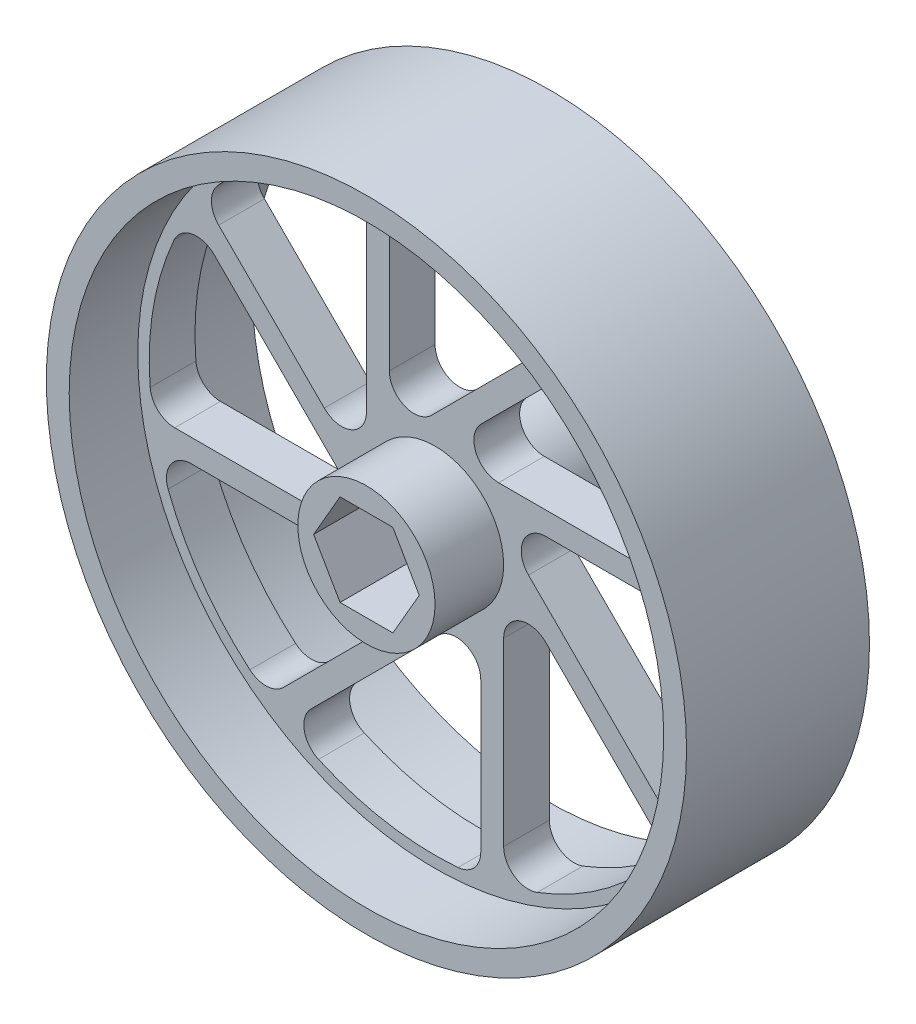
SolidWorks part; units mm, degrees
material "6061-T6 (SS)"
ref_plane "Front Plane" through (0, 0, 0) normal (0, 0, 1) x (1, 0, 0)
ref_plane "Top Plane" through (0, 0, 0) normal (0, 1, 0) x (1, 0, 0)
ref_plane "Right Plane" through (0, 0, 0) normal (1, 0, 0) x (0, 0, -1)
sketch "Sketch1" plane through (0, 0, 0) normal (0, 0, 1) x (1, 0, 0)
  line L1 (3.6662, -6.35) -> (7.3323, 0)
  line L2 (7.3323, 0) -> (3.6662, 6.35)
  line L3 (3.6662, 6.35) -> (-3.6662, 6.35)
  line L4 (-3.6662, 6.35) -> (-7.3323, 0)
  line L5 (-7.3323, 0) -> (-3.6662, -6.35)
  line L6 (-3.6662, -6.35) -> (3.6662, -6.35)
  circle A0 centre (0, 0) radius 44.45
  circle A1 centre (0, 0) radius 6.35 construction
  dimension "D1" = 88.9
  dimension "D2" = 12.7
extrude "Boss-Extrude1" add sketch "Sketch1" along normal mid plane 25.4
sketch "Sketch2" plane through (0, 0, 12.7) normal (0, 0, 1) x (1, 0, 0)
  circle A0 centre (0, 0) radius 9.525
  circle A1 centre (0, 0) radius 41.275
  circle A2 centre (0, 0) radius 44.45 construction
  dimension "D1" = 3.175
  dimension "D2" = 19.05
extrude "Cut-Extrude1" cut sketch "Sketch2" against normal through all
sketch "Sketch4" plane through (0, 0, 0) normal (0, 0, 1) x (1, 0, 0)
  line L0 (-9.525, 0) -> (-9.525, 40.1609)
  line L1 (-6.35, 7.0995) -> (-6.35, 40.7836)
  circle A2 centre (0, 0) radius 9.525 construction
  circle A3 centre (0, 0) radius 41.275 construction
  arc A4 (-6.35, 40.7836) -> (-9.525, 40.1609) centre (0, 0) ccw
  arc A5 (-6.35, 7.0995) -> (-9.525, 0) centre (0, 0) ccw
  dimension "D1" = 3.175
extrude "Boss-Extrude2" add sketch "Sketch4" along normal mid plane 6.35
sketch "Sketch5" plane through (0, 0, 3.175) normal (0, 0, 1) x (1, 0, 0)
  circle A0 centre (0, 0) radius 41.275
  circle A1 centre (0, 0) radius 39.6875
  circle A2 centre (0, 0) radius 41.275 construction
  circle A3 centre (0, 0) radius 44.45 construction
  dimension "D1" = 4.7625
extrude "Boss-Extrude3" add sketch "Sketch5" against normal up to surface (6.35 mm away) up to face at (-8.1284, 22.1035, -3.175)
fillet "Fillet1" radius 3.429 2 edges at (-9.525, 38.5275, 0) (-6.35, 39.1762, 0)
pattern_circular "CirPattern1" count 8 over 360 about axis through (0, 0, 12.7) along (0, 0, -1) of "Boss-Extrude2", "Fillet1"
fillet "Fillet2" radius 3.429 8 edges at (0.5447, 9.525, 0) (-6.35, 7.1204, 0) (-9.525, 0.5447, 0) (-7.1204, -6.35, 0) (-0.5447, -9.525, 0) (6.35, -7.1204, 0) (9.525, -0.5447, 0) (7.1204, 6.35, 0)
